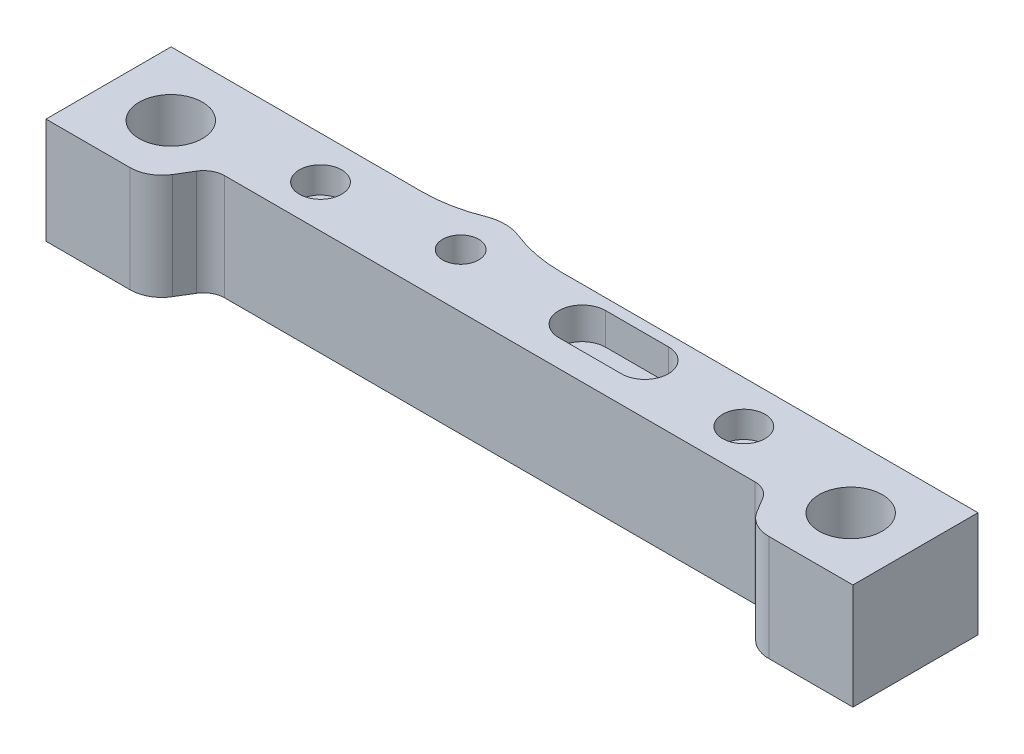
SolidWorks part; units mm, degrees
ref_plane "Front Plane" through (0, 0, 0) normal (0, 0, 1) x (1, 0, 0)
ref_plane "Top Plane" through (0, 0, 0) normal (0, 1, 0) x (1, 0, 0)
ref_plane "Right Plane" through (0, 0, 0) normal (1, 0, 0) x (0, 0, -1)
sketch "Sketch1" plane through (0, 0, 0) normal (0, 1, 0) x (1, 0, 0)
  line L0 (-38.12, 8.01) -> (-14.4092, 8.01)
  line L1 (38.12, 8.01) -> (38.12, -3.81)
  line L2 (38.12, -3.81) -> (28.4783, -3.81)
  line L3 (28.4783, -3.81) -> (26.1783, 0)
  line L4 (26.1783, 0) -> (-26.1783, 0)
  line L5 (-26.1783, 0) -> (-28.4783, -3.81)
  line L6 (-28.4783, -3.81) -> (-38.12, -3.81)
  line L7 (-38.12, -3.81) -> (-38.12, 8.01)
  line L8 (0, -55) -> (0, 55) construction
  line L9 (-20, 8.01) -> (-20, 0) construction
  line L10 (3.9921, 4.745) -> (9.9121, 4.745) construction
  line L11 (3.9921, 6.96) -> (9.9121, 6.96)
  line L12 (3.9921, 2.53) -> (9.9121, 2.53)
  line L14 (-1.2892, 8.01) -> (38.12, 8.01)
  circle A0 centre (-32.12, 1.98) radius 2.99
  circle A1 centre (32.12, 1.98) radius 2.99
  circle A2 centre (-20, 4.005) radius 2
  circle A3 centre (20, 4.005) radius 2
  arc A4 (3.9921, 6.96) -> (3.9921, 2.53) centre (3.9921, 4.745) ccw
  arc A5 (9.9121, 2.53) -> (9.9121, 6.96) centre (9.9121, 4.745) ccw
  circle A6 centre (-7.8492, 5.1) radius 1.7
  arc A7 (-9.4092, 8.978) -> (-6.2892, 8.978) centre (-7.8492, 5.1) cw
  arc A8 (-6.2892, 8.978) -> (-1.2892, 8.01) centre (-1.2892, 21.4074) ccw
  arc A9 (-9.4092, 8.978) -> (-14.4092, 8.01) centre (-14.4092, 21.4074) cw
  point P2 (0, 0)
  point P21 (-20, 4.005)
  point P24 (6.9521, 4.745)
  point P47 (-7.8492, 9.28)
  dimension "D1" = 5.98
  dimension "D7" = 5.92
  dimension "D9" = 6
  dimension "D10" = 5.79
  dimension "D11" = 3.4
  dimension "D12" = 2.48
  dimension "D13" = 12.2
  dimension "D14" = 4
  dimension "D15" = 10.115
  dimension "D16" = 9.28
  dimension "D18" = 6.11
  dimension "D2" = 6.03
  dimension "D3" = 8.01
  dimension "D4" = 40
  dimension "D5" = 64.24
  dimension "D6" = 4.43
  dimension "D8" = 1.05
  dimension "D17" = 2.3
  dimension "D19" = 5
extrude "Boss-Extrude1" add sketch "Sketch1" against normal blind 10 contours A7 A9 L0 L7 L6 L5 L4 L3 L2 L1 L14 A8 A3 A2 A0 A1 A5 L12 A4 L11 A6 | A2 | A6 | A0 | L12 A5 L11 A4 | A3 | A1 region at (-0.4788, 0, -3.3409) region at (6.9521, 0, -4.745) region at (-32.12, 0, -1.98) region at (32.12, 0, -1.98) region at (-20, 0, -4.005) region at (20, 0, -4.005) region at (-7.8492, 0, -5.1)
fillet "Fillet1" radius 2 2 edges at (26.1783, -5, 0) (-26.1783, -5, 0)
fillet "Fillet2" radius 3 2 edges at (28.4783, -5, 3.81) (-28.4783, -5, 3.81)
extrude "Cut-Extrude3" cut sketch "Sketch1<4>" against normal blind 5.07 contours A1 | A0 region at (32.12, 0, -1.98)
sketch "Sketch1<4>" plane through (0, 0, 0) normal (0, 1, 0) x (1, 0, 0) same geometry as "Sketch1"
extrude "Cut-Extrude4" cut sketch "Sketch1<5>" against normal blind 2.48 contours A2 | A3 region at (-20, 0, -4.005) region at (20, 0, -4.005)
sketch "Sketch1<5>" plane through (0, 0, 0) normal (0, 1, 0) x (1, 0, 0) same geometry as "Sketch1"
extrude "Cut-Extrude5" cut sketch "Sketch1<6>" against normal blind 3 contours L12 A5 L11 A4 region at (6.9521, 0, -4.745)
sketch "Sketch1<6>" plane through (0, 0, 0) normal (0, 1, 0) x (1, 0, 0) same geometry as "Sketch1"
extrude "Cut-Extrude6" cut sketch "Sketch1<7>" against normal up to surface (10 mm away) contours A6 region at (-7.8492, 0, -5.1) up to face at (-1.9623, -10, -1.7312)
sketch "Sketch1<7>" plane through (0, 0, 0) normal (0, 1, 0) x (1, 0, 0) same geometry as "Sketch1"
sketch "Sketch4" plane through (0, 0, 0) normal (0, 1, 0) x (1, 0, 0)
  line L0 (0, -55) -> (0, 55) construction
  circle A0 centre (-20, 4.005) radius 1.25
  circle A1 centre (20, 4.005) radius 1.25
  dimension "D1" = 2.5
extrude "Cut-Extrude7" cut sketch "Sketch4" against normal up to surface (10 mm away) contours A0 | A1 region at (-20, 0, -4.005) region at (20, 0, -4.005) up to face at (-7.8492, -10, -3.4)
sketch "Sketch5" plane through (0, -10, 0) normal (0, -1, 0) x (1, 0, 0)
  line L0 (0, -55) -> (0, 55) construction
  circle A0 centre (20, -4.005) radius 2.725
  circle A1 centre (-20, -4.005) radius 2.725
  dimension "D1" = 5.45
extrude "Cut-Extrude8" cut sketch "Sketch5" against normal blind 2.8
